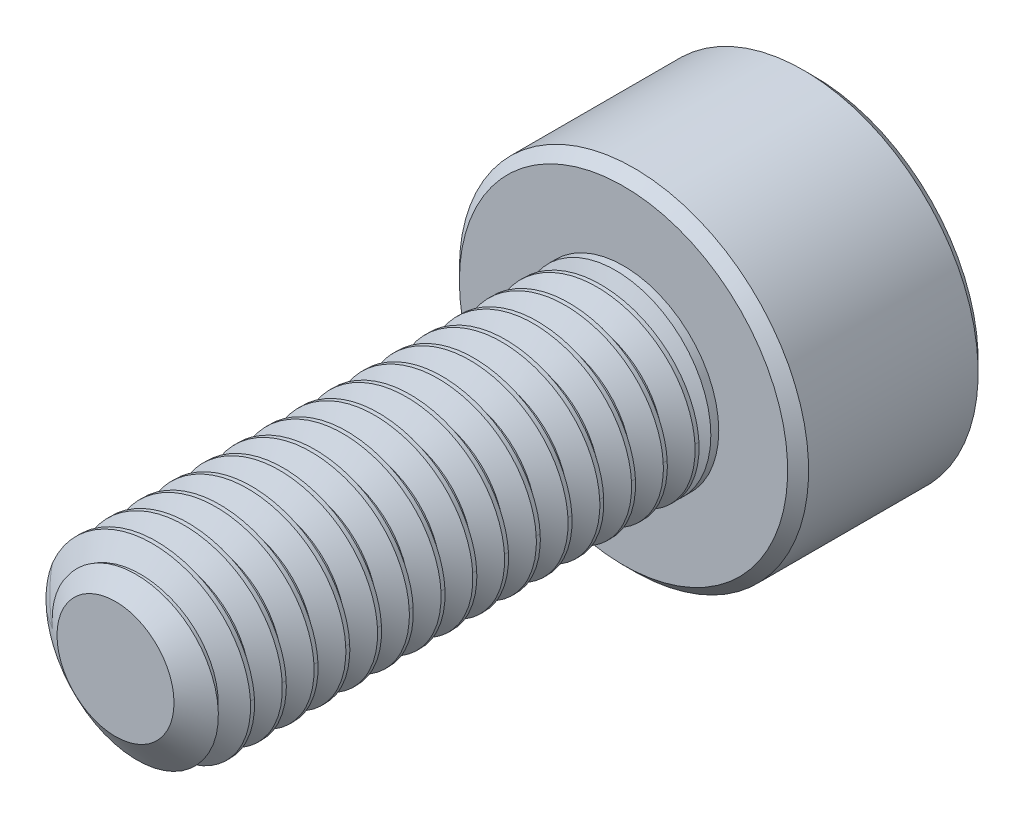
SolidWorks part; units mm, degrees
ref_plane "Front Plane" through (0, 0, 0) normal (0, 0, 1) x (1, 0, 0)
ref_plane "Top Plane" through (0, 0, 0) normal (0, 1, 0) x (1, 0, 0)
ref_plane "Right Plane" through (0, 0, 0) normal (1, 0, 0) x (0, 0, -1)
sketch "Sketch1" plane through (0, 0, 0) normal (0, 0, 1) x (1, 0, 0)
  circle A0 centre (0, 0) radius 1.5
  dimension "OD" = 3
extrude "Extrude1" add sketch "Sketch1" against normal blind 8
sketch "Sketch2" plane through (0, 0, 0) normal (0, 0, 1) x (1, 0, 0)
  circle A0 centre (0, 0) radius 1.5 construction
  circle A1 centre (0, 0) radius 1.5
curve "Helix/Spiral1" pitch 0.5 height 8.5 radius 1.5 centre (0, 0, 0) axis (0, 0, -1) start towards (0, 1, 0) parameters "pitch"=0.5
sketch "Sketch3" plane through (0, 0, 0) normal (1, 0, 0) x (0, 0, -1)
  line L0 (-0.4375, 1.5) -> (-0.25, 1.1752)
  line L1 (-0.25, 1.1752) -> (-0.1875, 1.1752)
  line L2 (-0.1875, 1.1752) -> (0, 1.5)
  line L3 (-0.4375, 1.5) -> (0, 1.5)
  line L4 (-0.2187, 1.5) -> (-0.2187, 1.1752) construction
  line L5 (-0.3437, 1.3376) -> (-0.0937, 1.3376) construction
  line L6 (0, 1.5) -> (0, -1.5) construction
  line L7 (0, -1.5) -> (8, -1.5) construction
  point P11 (2.25, -1.5)
  dimension "D1" = 0.0625
  dimension "D2" = 0.25
  dimension "D3" = 60
  dimension "D4" = 2.25
sweep "Cut-Sweep1" cut profiles "Sketch3" path "Helix/Spiral1" align with end faces yes
sketch "Sketch4" plane through (0, 0, 0) normal (1, 0, 0) x (0, 0, -1)
  line L0 (0.4053, 1.5) -> (0, 0.9212)
  line L1 (0, 0.9212) -> (0, 1.5)
  line L2 (0.4053, 1.5) -> (0, 1.5)
  line L3 (-0.4375, 1.5) -> (0, 1.5) construction
  line L4 (0, 0) -> (7.0209, 0) construction
  dimension "D1" = 55
  dimension "D2" = 0.254
revolve "Cut-Revolve1" cut sketch "Sketch4" angle 360 about L4
sketch "Sketch5" plane through (0, 0, 0) normal (1, 0, 0) x (0, 0, -1)
  line L0 (8, -1.1822) -> (8, 1.0703) construction
  line L1 (8, 1.5) -> (0.1203, 1.5)
  line L2 (8, 1.5) -> (8, 0)
  line L3 (8, 0) -> (0.0001, 0)
  line L4 (0.0001, 1.1698) -> (0.0001, 0)
  line L5 (0.1203, 1.5) -> (0.0001, 1.1698)
  line L6 (0, 0) -> (9.9695, 0) construction
  point P3 (0.0001, 1.5)
  point P10 (0.0001, 1.5)
  dimension "D1" = 0.3302
  dimension "Thread min" = 0.0001
  dimension "D3" = 20
revolve "partially thread" [suppressed] add sketch "Sketch5" angle 360 about L6
sketch "Sketch6" plane through (0, 0, -8) normal (0, 0, -1) x (-1, 0, 0)
  circle A0 centre (0, 0) radius 2.75
  dimension "head dia" = 5.5
extrude "Extrude2" add sketch "Sketch6" along normal blind 3
sketch "Sketch7" plane through (0, 0, -11) normal (0, 0, -1) x (-1, 0, 0)
  line L1 (0, 1.4434) -> (-1.25, 0.7217)
  line L2 (-1.25, 0.7217) -> (-1.25, -0.7217)
  line L3 (-1.25, -0.7217) -> (0, -1.4434)
  line L4 (0, -1.4434) -> (1.25, -0.7217)
  line L5 (1.25, -0.7217) -> (1.25, 0.7217)
  line L6 (1.25, 0.7217) -> (0, 1.4434)
  circle A0 centre (0, 0) radius 1.25 construction
  dimension "hex dia" = 2.5
extrude "Cut-Extrude1" cut sketch "Sketch7" against normal blind 1.875
sketch "Sketch8" plane through (0, 0, -11) normal (0, 0, -1) x (-1, 0, 0)
  circle A0 centre (0, 0) radius 1.4434
extrude "Cut-Extrude2" cut sketch "Sketch8" against normal through all draft 45
chamfer "Chamfer1" distance 0.165 angle 45 2 edges at (-2.75, 0, -11) (-2.75, 0, -8)
sketch "Sketch9" plane through (0, 0, 0) normal (1, 0, 0) x (0, 0, -1)
  line L0 (0, 1.5) -> (0, -1.5) construction
  line L1 (2.75, 1.5) -> (2.75, -1.5) construction
  dimension "D1" = 2.75
sketch "Sketch10" plane through (0, 0, 0) normal (1, 0, 0) x (0, 0, -1)
  line L0 (8, 1.5) -> (8, 0)
  line L1 (8, 1.5) -> (7.875, 1.5)
  line L2 (7.875, 1.5) -> (7.2537, 0)
  line L3 (8, 0) -> (7.2537, 0)
  line L4 (8, 2.585) -> (8, -2.585) construction
  dimension "D1" = 22.5
  dimension "D2" = 0.125
revolve "Revolve1" add sketch "Sketch10" angle 360 about L3
ref_axis "Axis1" through (0, 0, -10.835) along (0, 0, 1)
equation "\"D3@Helix/Spiral1\" = \"screw length@Extrude1\"+\"pitch@Helix/Spiral1\""
equation "\"D1@Sketch3\" = \"pitch@Helix/Spiral1\"*.125"
equation "\"D2@Sketch3\" = \"pitch@Helix/Spiral1\"*.5"
equation "\"D1@Cut-Extrude1\" = \"hex dia@Sketch7\"*.75"
equation "\"D1@Chamfer1\" = \"head dia@Sketch6\"*.03"
equation "\"D1@Sketch9\" = \"pitch@Helix/Spiral1\"*5.5"
equation "\"D2@Sketch10\" = \"pitch@Helix/Spiral1\"*.25"
equation "\"D4@Sketch3\" = \"pitch@Helix/Spiral1\"*4.50"
